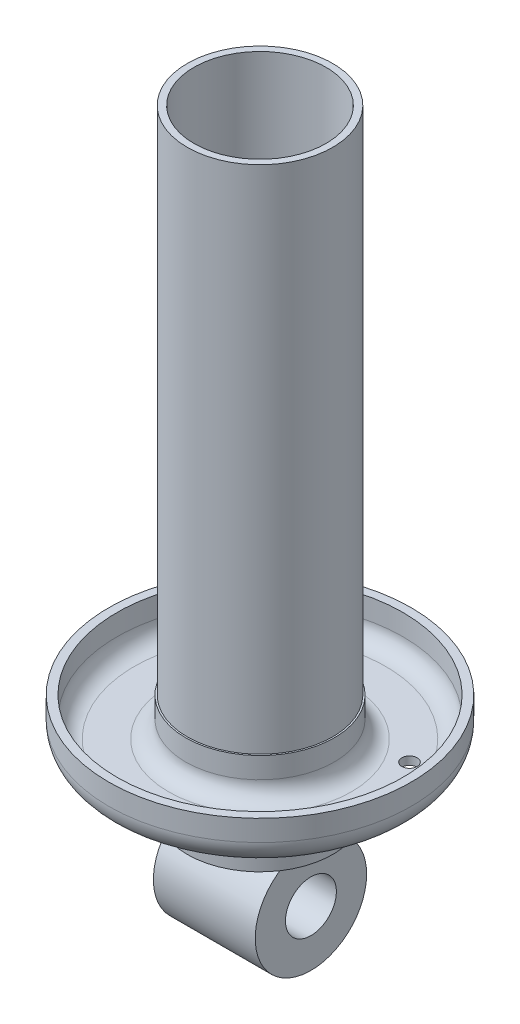
SolidWorks part; units mm, degrees
ref_plane "Front Plane" through (0, 0, 0) normal (0, 0, 1) x (1, 0, 0)
ref_plane "Top Plane" through (0, 0, 0) normal (0, 1, 0) x (1, 0, 0)
ref_plane "Right Plane" through (0, 0, 0) normal (1, 0, 0) x (0, 0, -1)
sketch "Sketch1" plane through (0, 0, 0) normal (0, 1, 0) x (1, 0, 0)
  circle A0 centre (0, 0) radius 47.5
  dimension "D1" = 95
extrude "Boss-Extrude2" add sketch "Sketch1" along normal blind 14.6
sketch "Sketch4" plane through (0, 14.6, 0) normal (0, 1, 0) x (1, 0, 0)
  circle A0 centre (0, 0) radius 22.85
  dimension "D1" = 45.7
extrude "Boss-Extrude3" add sketch "Sketch4" along normal blind 10.4
sketch "Sketch5" plane through (0, 25, 0) normal (0, 1, 0) x (1, 0, 0)
  circle A0 centre (0, 0) radius 20.75
  dimension "D1" = 41.5
extrude "Cut-Extrude3" cut sketch "Sketch5" against normal through all contours A0
fillet "Fillet2" radius 8 1 edges at (0, 0, 47.5)
fillet "Fillet3" radius 8 1 edges at (0, 0, 20.75)
shell "Shell2" thickness 2.6 removed face at (0, 14.6, 22.85)
sketch "Sketch6" plane through (0, 0, 0) normal (0, -1, 0) x (-1, 0, 0)
  circle A0 centre (0, -34.3843) radius 2.4
  dimension "D1" = 4.8
extrude "Cut-Extrude4" cut sketch "Sketch6" against normal through all
pattern_circular "CirPattern1" count 3 over 360 about axis through (0, 0, 0) along (0, 1, 0) of "Cut-Extrude4"
sketch "Sketch7" plane through (0, 25, 0) normal (0, 1, 0) x (1, 0, 0)
  circle A0 centre (0, 0) radius 22.85 construction
  circle A1 centre (0, 0) radius 22.85
  circle A2 centre (0, 0) radius 20.75 construction
  circle A3 centre (0, 0) radius 20.75
  dimension "D1" = 2.1
extrude "Boss-Extrude4" add sketch "Sketch7" along normal blind 150
extrude "Boss-Extrude5" add sketch "Sketch4<2>" against normal blind 32
sketch "Sketch4<2>" plane through (0, 14.6, 0) normal (0, 1, 0) x (1, 0, 0) same geometry as "Sketch4"
sketch "Sketch8" plane through (0, 0, 0) normal (1, 0, 0) x (0, 0, -1)
  line L0 (-22.85, -17.4) -> (22.85, -17.4) construction
  circle A0 centre (0, -34.9) radius 17.5
  circle A1 centre (0, -34.9) radius 8
  dimension "D1" = 35
  dimension "D2" = 16
extrude "Boss-Extrude6" add sketch "Sketch8" along normal mid plane 32 separate body
